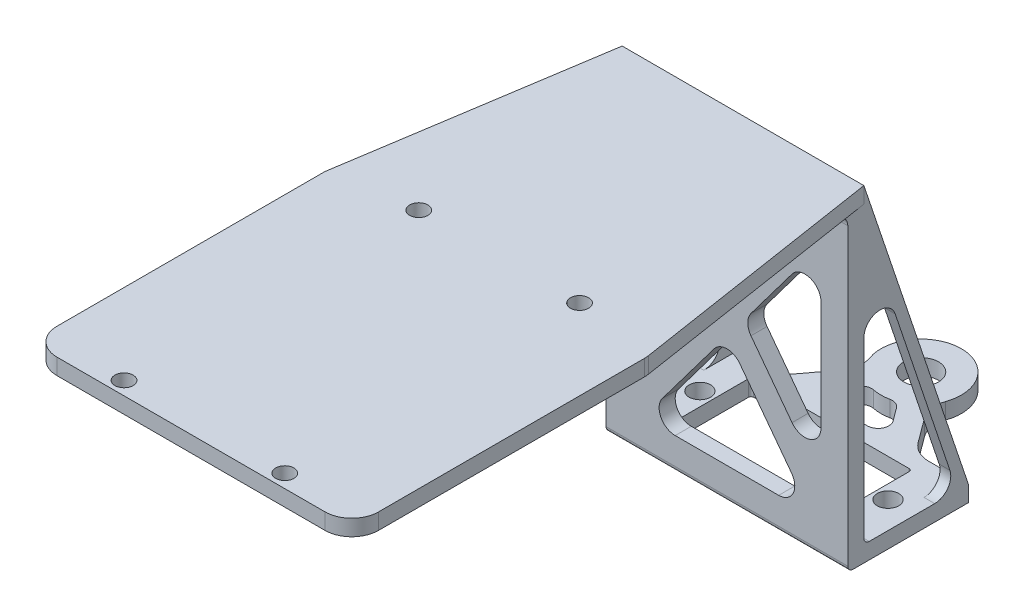
SolidWorks part; units mm, degrees
ref_plane "Front Plane" through (0, 0, 0) normal (0, 0, 1) x (1, 0, 0)
ref_plane "Top Plane" through (0, 0, 0) normal (0, 1, 0) x (1, 0, 0)
ref_plane "Right Plane" through (0, 0, 0) normal (1, 0, 0) x (0, 0, -1)
sketch "Sketch1" plane through (0, 0, 0) normal (0, 1, 0) x (1, 0, 0)
  line L0 (0, 22.75) -> (0, -22.75) construction
  line L1 (-22.55, 10) -> (22.55, 10)
  line L2 (-22.55, 10) -> (-22.55, -36.2398)
  line L3 (-22.55, -36.2398) -> (22.55, -36.2398)
  line L4 (22.55, 10) -> (22.55, -36.2398)
  line L5 (0, -41.046) -> (0, -71.5139) construction
  line L6 (-17.55, -23.7398) -> (17.55, -23.7398) construction
  line L7 (-19.9, -23.7398) -> (19.9, -23.7398) construction
  line L8 (-19.9, -17.2398) -> (19.9, -17.2398) construction
  line L9 (-19.9, -17.2398) -> (-19.9, -30.2398) construction
  line L10 (-19.9, -30.2398) -> (19.9, -30.2398) construction
  line L11 (19.9, -17.2398) -> (19.9, -30.2398) construction
  line L12 (0, -15.2398) -> (0, 15.2398)
  line L13 (-22.55, -36.2398) -> (22.55, -36.2398)
  line L14 (-22.55, -36.2398) -> (-22.55, -33.2398)
  line L15 (-22.55, -33.2398) -> (22.55, -33.2398) construction
  line L16 (22.55, -36.2398) -> (22.55, -33.2398)
  line L17 (15, -30.7398) -> (-15, -30.7398)
  line L18 (15, -30.7398) -> (15, -16.7398)
  line L19 (15, -16.7398) -> (-15, -16.7398)
  line L20 (-15, -30.7398) -> (-15, -16.7398)
  line L21 (15, -30.7398) -> (-15, -16.7398) construction
  line L22 (15, -16.7398) -> (-15, -30.7398) construction
  line L23 (15.0921, 2.1162) -> (-15.0921, -2.1162)
  circle A0 centre (0, 0) radius 3.25
  circle A2 centre (-17.55, -23.7398) radius 2
  circle A3 centre (17.55, -23.7398) radius 2
  point P23 (0, -23.7398)
  dimension "D1" = 6.5
  dimension "D8" = 4
  dimension "D2" = 35.1
  dimension "D3" = 45.5
  dimension "D4" = 10
  dimension "D5" = 17.55
  dimension "D6" = 13
  dimension "D7" = 39.8
  dimension "D9" = 19.9
  dimension "D10" = 3
  dimension "D11" = 3
  dimension "D12" = 1.5
  dimension "D13" = 5
  dimension "D14" = 5
  dimension "D15" = 30
  dimension "D16" = 14
  dimension "D17" = 20
  dimension "D18" = 23
extrude "Boss-Extrude1" add sketch "Sketch1" along normal blind 3
sketch "Sketch2" plane through (0, 3, 0) normal (0, 1, 0) x (1, 0, 0)
  line L0 (22.55, 10) -> (22.55, -36.2398) construction
  line L1 (-22.55, -36.2398) -> (22.55, -36.2398)
  line L2 (-22.55, -36.2398) -> (-22.55, -33.2398)
  line L3 (-22.55, -33.2398) -> (22.55, -33.2398)
  line L4 (22.55, -36.2398) -> (22.55, -33.2398)
  line L5 (-24.6944, -15.2398) -> (24.6944, -15.2398) construction
  line L8 (-24.6944, -13.7398) -> (24.6944, -13.7398)
  line L11 (-24.6944, -16.7398) -> (24.6944, -16.7398)
  line L14 (-22.55, 10) -> (-22.55, -36.2398)
  line L15 (22.55, -36.2398) -> (22.55, 10)
  line L16 (22.55, 10) -> (-22.55, 10)
  line L17 (15, -16.7398) -> (-15, -16.7398) construction
  line L18 (-17.55, -23.7398) -> (0, 0) construction
  line L19 (-19.1582, -22.5508) -> (-1.6082, 1.1889)
  line L20 (-15.9418, -24.9287) -> (1.6082, -1.1889)
  line L21 (0, 0) -> (17.55, -23.7398) construction
  line L22 (1.6082, 1.1889) -> (19.1582, -22.5508)
  line L23 (-1.6082, -1.1889) -> (15.9418, -24.9287)
  circle A0 centre (0, 0) radius 7.5
  arc A9 (-24.6944, -13.7398) -> (-24.6944, -16.7398) centre (-24.6944, -15.2398) ccw
  arc A10 (24.6944, -16.7398) -> (24.6944, -13.7398) centre (24.6944, -15.2398) ccw
  circle A11 centre (-17.55, -23.7398) radius 7.5
  circle A12 centre (17.55, -23.7398) radius 7.5
  arc A13 (-19.1582, -22.5508) -> (-15.9418, -24.9287) centre (-17.55, -23.7398) ccw
  arc A14 (1.6082, -1.1889) -> (-1.6082, 1.1889) centre (0, 0) ccw
  arc A15 (1.6082, 1.1889) -> (-1.6082, -1.1889) centre (0, 0) ccw
  arc A16 (15.9418, -24.9287) -> (19.1582, -22.5508) centre (17.55, -23.7398) ccw
  point P6 (0, -15.2398)
  point P25 (-8.775, -11.8699)
  point P30 (8.775, -11.8699)
  line M20 (22.55, -36.2398) -> (22.55, 10)
  line M21 (22.55, 10) -> (-22.55, 10)
  line M22 (-22.55, 10) -> (-22.55, -36.2398)
  dimension "D1" = 1.5
  dimension "D3" = 15
  dimension "D4" = 2
  dimension "D2" = 3
extrude "Cut-Extrude1" cut sketch "Sketch2" against normal blind 3 contours A0 L22 L8 L19 M20 M21 M22 | A0 L20 L8 L23
fillet "Fillet1" radius 5 4 edges at (12.6445, 1.5, 13.7398) (-12.6445, 1.5, 13.7398) (5.9053, 1.5, 4.6236) (-5.9053, 1.5, 4.6236)
fillet "Fillet2" radius 2 4 edges at (7.6702, 1.5, 13.7398) (-7.6702, 1.5, 13.7398) (2.6888, 1.5, 7.0015) (-2.6888, 1.5, 7.0015)
sketch "Sketch3" plane through (0, 3, 0) normal (0, 1, 0) x (1, 0, 0)
  line L0 (22.55, -13.7398) -> (22.55, -36.2398) construction
  line L1 (-22.55, -36.2398) -> (22.55, -36.2398)
  line L2 (-22.55, -36.2398) -> (-22.55, -33.2398)
  line L3 (-22.55, -33.2398) -> (22.55, -33.2398)
  line L4 (22.55, -36.2398) -> (22.55, -33.2398)
  dimension "D1" = 3
extrude "Boss-Extrude2" add sketch "Sketch3" along normal blind 58
fillet "Fillet3" radius 0.5 4 edges at (-15, 1.5, 30.7398) (15, 1.5, 30.7398) (15, 1.5, 16.7398) (-15, 1.5, 16.7398)
fillet "Fillet4" radius 1 2 edges at (0, 3, 33.2398) (0, 0, 36.2398)
sketch "Sketch4" plane through (0, 0, 36.2398) normal (0, 0, 1) x (1, 0, 0)
  line L0 (22.55, 61) -> (22.55, 1) construction
  line L1 (-22.55, 61) -> (22.55, 61)
  line L2 (-22.55, 61) -> (-22.55, 56)
  line L3 (-22.55, 56) -> (22.55, 56)
  line L4 (22.55, 61) -> (22.55, 56)
  line L5 (-22.55, 1) -> (22.55, 1) construction
  line L6 (-22.55, 61) -> (-17.55, 61)
  line L7 (-22.55, 61) -> (-22.55, 1)
  line L8 (-22.55, 1) -> (-17.55, 1)
  line L9 (-17.55, 61) -> (-17.55, 1)
  line L10 (-22.55, 1) -> (22.55, 61) construction
  line L11 (-22.55, 1) -> (22.55, 1)
  line L12 (-22.55, 1) -> (-22.55, 6)
  line L13 (-22.55, 6) -> (22.55, 6)
  line L14 (22.55, 1) -> (22.55, 6)
  line L15 (22.55, 1) -> (17.55, 1)
  line L16 (22.55, 1) -> (22.55, 61)
  line L17 (22.55, 61) -> (17.55, 61)
  line L18 (17.55, 1) -> (17.55, 61)
  line L19 (-24.5484, 2.5021) -> (20.5516, 62.5021)
  line L20 (-20.5516, -0.5021) -> (24.5484, 59.4979)
  line L21 (-22.55, 61) -> (22.55, 1) construction
  line L22 (-20.5516, 62.5021) -> (24.5484, 2.5021)
  line L23 (-24.5484, 59.4979) -> (20.5516, -0.5021)
  arc A0 (-24.5484, 2.5021) -> (-20.5516, -0.5021) centre (-22.55, 1) ccw
  arc A1 (24.5484, 59.4979) -> (20.5516, 62.5021) centre (22.55, 61) ccw
  arc A2 (-20.5516, 62.5021) -> (-24.5484, 59.4979) centre (-22.55, 61) ccw
  arc A3 (20.5516, -0.5021) -> (24.5484, 2.5021) centre (22.55, 1) ccw
  point P17 (0, 31)
  point P22 (0, 31)
  dimension "D5" = 2.5
  dimension "D6" = 2.5
  dimension "D1" = 5
  dimension "D2" = 5
  dimension "D3" = 5
  dimension "D4" = 5
extrude "Cut-Extrude2" cut sketch "Sketch4" against normal blind 10 contours L23 L9 L19 | L3 L22 L19 | L20 L22 L18 | L23 L20 L13
fillet "Fillet5" radius 3 12 edges at (-15.6642, 6, 34.7398) (0, 26.8392, 34.7398) (15.6642, 6, 34.7398) (17.55, 11.8126, 34.7398) (3.1275, 31, 34.7398) (17.55, 50.1874, 34.7398) (-15.6642, 56, 34.7398) (15.6642, 56, 34.7398) (0, 35.1608, 34.7398) (-17.55, 11.8126, 34.7398) (-3.1275, 31, 34.7398) (-17.55, 50.1874, 34.7398)
sketch "Sketch5" plane through (22.55, 0, 0) normal (1, 0, 0) x (0, 0, -1)
  line L0 (-33.2398, 61) -> (-13.7398, 3)
  line L1 (-33.2398, 54.7241) -> (-15.8498, 3)
  line L3 (-33.2398, 61) -> (-33.2398, 54.7241)
  line L4 (-15.8498, 3) -> (-13.7398, 3)
  dimension "D1" = 2
extrude "Boss-Extrude3" add sketch "Sketch5" against normal blind 2
ref_plane "Plane1" through (0, 0, 0) normal (-1, 0, 0) x (0, 0, 1)
mirror "Mirror1" about plane through (0, 0, 0) normal (-1, 0, 0) of "Boss-Extrude3"
fillet "Fillet6" radius 3 4 edges at (21.55, 3, 15.8498) (21.55, 54.7241, 33.2398) (-21.55, 54.7241, 33.2398) (-21.55, 3, 15.8498)
sketch "Sketch6" plane through (0, 0, 36.2398) normal (0, 0, 1) x (1, 0, 0)
  line L0 (22.55, 61) -> (22.55, 1) construction
  line L1 (-22.55, 61) -> (22.55, 61)
  line L2 (-22.55, 61) -> (-22.55, 58)
  line L3 (-22.55, 58) -> (22.55, 58)
  line L4 (22.55, 61) -> (22.55, 58)
  dimension "D1" = 3
extrude "Boss-Extrude4" add sketch "Sketch6" along normal blind 45
fillet "Fillet8" radius 2 1 edges at (0, 58, 36.2398)
sketch "Sketch7" plane through (0, 58, 0) normal (0, -1, 0) x (1, 0, 0)
  line L0 (-19.043, 35.2398) -> (-19.043, 41.2398)
  line L1 (22.55, 35.2398) -> (-22.55, 35.2398) construction
  line L2 (-22.55, 81.2398) -> (-22.55, 38.2398) construction
  line L3 (-22.55, 76.2398) -> (22.55, 76.2398)
  line L4 (-22.55, 76.2398) -> (-22.55, 81.2398)
  line L5 (-22.55, 81.2398) -> (22.55, 81.2398)
  line L6 (22.55, 76.2398) -> (22.55, 81.2398)
  line L7 (22.55, 81.2398) -> (22.55, 38.2398) construction
  line L8 (-19.043, 41.2398) -> (-19.043, 76.2398)
  line L9 (-15, 78.7398) -> (15, 78.7398)
  line L10 (0, 13.475) -> (0, -13.475) construction
  circle A0 centre (-15, 78.7398) radius 1.7
  circle A1 centre (15, 78.7398) radius 1.7
  dimension "D4" = 3.4
  dimension "D5" = 3.4
  dimension "D1" = 6
  dimension "D2" = 5
  dimension "D3" = 35
  dimension "D6" = 30
  dimension "D7" = 2.5
  dimension "D8" = 15
extrude "Cut-Extrude3" cut sketch "Sketch7" against normal blind 10
sketch "Sketch9" plane through (0, 61, 0) normal (0, 1, 0) x (1, 0, 0)
  line L0 (-22.55, -33.2398) -> (-30, -81.2398)
  line L1 (22.55, -33.2398) -> (30, -81.2398)
  line L2 (-30, -81.2398) -> (30, -81.2398)
  line L3 (-30, -81.2398) -> (-30, -131.2398)
  line L4 (-30, -131.2398) -> (30, -131.2398)
  line L5 (30, -81.2398) -> (30, -131.2398)
  line L6 (0, -131.2398) -> (0, -81.2398)
  line L7 (0, 13.475) -> (0, -13.475) construction
  line L8 (22.55, -81.2398) -> (-22.55, -81.2398) construction
  line L9 (-22.55, -33.2398) -> (-22.55, -81.2398)
  line L10 (22.55, -33.2398) -> (22.55, -81.2398)
  line M10 (-22.55, -33.2398) -> (-22.55, -81.2398)
  line M11 (-22.55, -81.2398) -> (22.55, -81.2398)
  line M12 (22.55, -81.2398) -> (22.55, -33.2398)
  dimension "D1" = 60
  dimension "D2" = 50
extrude "Boss-Extrude5" add sketch "Sketch9" against normal blind 3 contours L0 L2 M10 | L4 L6 L2 L3 M11 | L6 L4 L5 L2 | L2 L1 M12
sketch "Sketch10" plane through (0, 58, 0) normal (0, -1, 0) x (1, 0, 0)
  line L0 (30, 133.7398) -> (-30, 133.7398) construction
  line L1 (-30, 131.2398) -> (30, 131.2398)
  line L2 (-30, 131.2398) -> (-30, 136.2398)
  line L3 (-30, 136.2398) -> (30, 136.2398)
  line L4 (30, 131.2398) -> (30, 136.2398)
  line L5 (-24.4972, 136.2398) -> (-21.4972, 136.2398)
  line L6 (-24.4972, 136.2398) -> (-24.4972, 180.7022)
  line L7 (-24.4972, 180.7022) -> (-21.4972, 180.7022)
  line L8 (-21.4972, 136.2398) -> (-21.4972, 180.7022)
  line L9 (7.5863, 136.2398) -> (10.5863, 136.2398)
  line L10 (7.5863, 136.2398) -> (7.5863, 180.7022)
  line L11 (7.5863, 180.7022) -> (10.5863, 180.7022)
  line L12 (10.5863, 136.2398) -> (10.5863, 180.7022)
  line L13 (0, 136.2398) -> (0, 131.2398) construction
  line L14 (15, 133.7398) -> (-15, 133.7398)
  circle A0 centre (15, 133.7398) radius 1.7
  circle A1 centre (-15, 133.7398) radius 1.7
  point P19 (-10.6417, 133.7398)
  point P20 (0, 133.7398)
  dimension "D4" = 3.4
  dimension "D1" = 3
  dimension "D2" = 3
  dimension "D3" = 5
  dimension "D5" = 30
extrude "Boss-Extrude6" add sketch "Sketch10" against normal blind 3
ref_plane "Plane2" through (10, 0, 0) normal (1, 0, 0) x (0, 0, -1)
fillet "Fillet12" radius 5 4 edges at (-30, 59.5, 81.2398) (-30, 59.5, 136.2398) (30, 59.5, 136.2398) (30, 59.5, 81.2398)
equation "\"30mmm\"=300"
